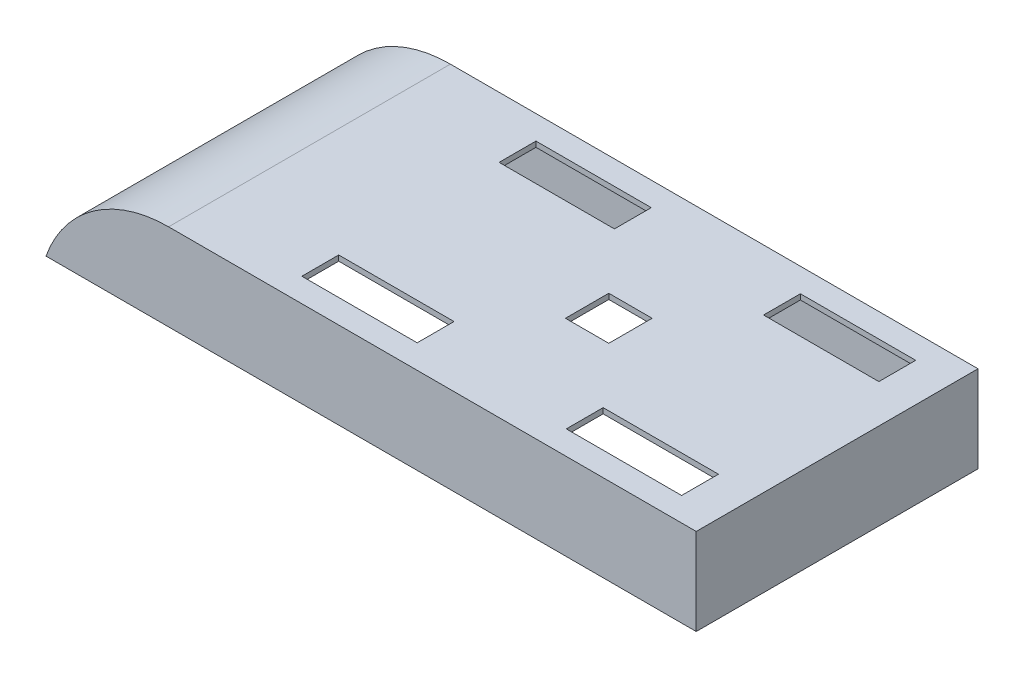
SolidWorks part; units mm, degrees
ref_plane "Front Plane" through (0, 0, 0) normal (0, 0, 1) x (1, 0, 0)
ref_plane "Top Plane" through (0, 0, 0) normal (0, 1, 0) x (1, 0, 0)
ref_plane "Right Plane" through (0, 0, 0) normal (1, 0, 0) x (0, 0, -1)
sketch "Sketch1" plane through (0, 0, 0) normal (0, 1, 0) x (1, 0, 0)
  line L1 (0, 0) -> (762, 0)
  line L2 (0, 0) -> (0, 330.2)
  line L3 (0, 330.2) -> (762, 330.2)
  line L4 (762, 0) -> (762, 330.2)
  dimension "D1" = 762
  dimension "D2" = 330.2
extrude "Boss-Extrude1" add sketch "Sketch1" along normal blind 101.6
fillet "Fillet1" radius 152.4 1 edges at (0, 101.6, -165.1)
shell "Shell1" thickness 6.35 removed face at (381, 0, -165.1)
sketch "Sketch3" plane through (0, 101.6, 0) normal (0, 1, 0) x (1, 0, 0)
  line L0 (271.9211, 27.935) -> (407.0491, 27.935)
  line L17 (407.0491, 27.935) -> (407.0491, 71.115)
  line L18 (143.6841, 165.1) -> (762, 165.1) construction
  line L19 (143.6841, 330.2) -> (143.6841, 0) construction
  line L20 (762, 0) -> (762, 330.2) construction
  line L21 (494.4251, 330.2) -> (494.4251, 0) construction
  line L23 (716.9291, 259.085) -> (581.8011, 259.085)
  line L24 (581.8011, 302.265) -> (581.8011, 259.085)
  line L25 (716.9291, 302.265) -> (581.8011, 302.265)
  line L26 (716.9291, 302.265) -> (716.9291, 259.085)
  line L27 (716.9291, 27.935) -> (716.9291, 71.115)
  line L28 (716.9291, 27.935) -> (581.8011, 27.935)
  line L29 (581.8011, 27.935) -> (581.8011, 71.115)
  line L30 (716.9291, 71.115) -> (581.8011, 71.115)
  line L42 (271.9211, 71.115) -> (407.0491, 71.115)
  line L43 (271.9211, 27.935) -> (271.9211, 71.115)
  line L44 (271.9211, 302.265) -> (271.9211, 259.085)
  line L45 (271.9211, 302.265) -> (407.0491, 302.265)
  line L46 (407.0491, 302.265) -> (407.0491, 259.085)
  line L47 (271.9211, 259.085) -> (407.0491, 259.085)
  line L52 (762, 330.2) -> (143.6841, 330.2) construction
  line L66 (469.0251, 139.7) -> (519.8251, 139.7)
  line L67 (469.0251, 139.7) -> (469.0251, 190.5)
  line L68 (469.0251, 190.5) -> (519.8251, 190.5)
  line L69 (519.8251, 139.7) -> (519.8251, 190.5)
  line L70 (494.4251, 190.5) -> (494.4251, 139.7) construction
  line L71 (469.0251, 165.1) -> (519.8251, 165.1) construction
  point P10 (649.3651, 259.085)
  point P11 (494.4251, 165.1)
  point P27 (494.4251, 165.1)
  dimension "D1" = 45.0709
  dimension "D2" = 154.94
  dimension "D3" = 43.18
  dimension "D4" = 135.128
  dimension "D5" = 50.8
  dimension "D6" = 50.8
  dimension "D7" = 274.33
extrude "Cut-Extrude1" cut sketch "Sketch3" against normal blind 127.762
